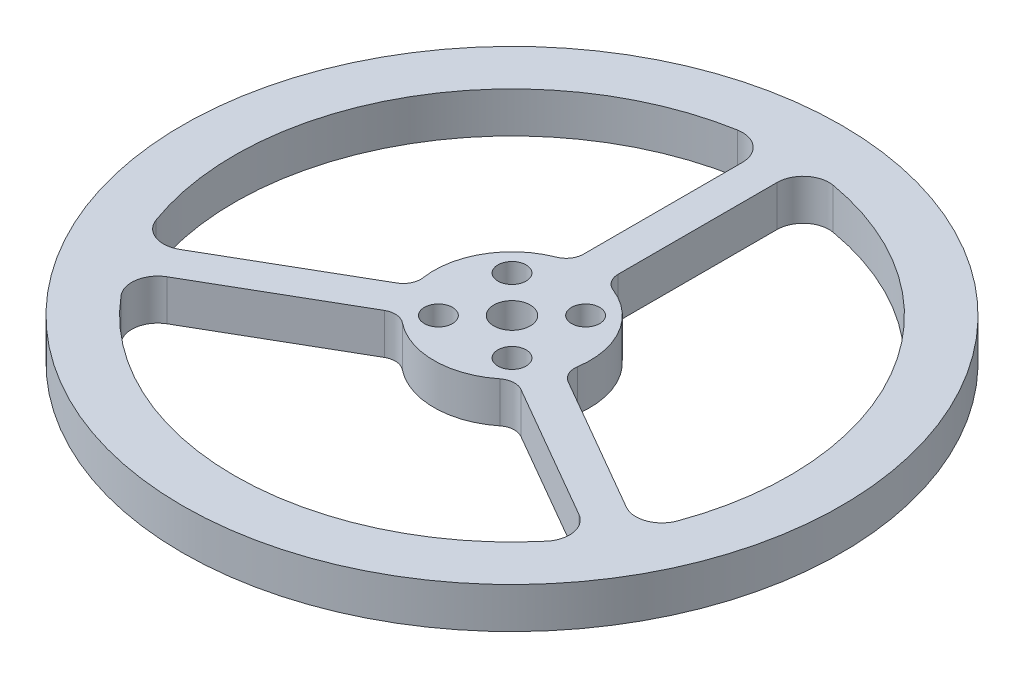
SolidWorks part; units mm, degrees
ref_plane "Front Plane" through (0, 0, 0) normal (0, 0, 1) x (1, 0, 0)
ref_plane "Top Plane" through (0, 0, 0) normal (0, 1, 0) x (1, 0, 0)
ref_plane "Right Plane" through (0, 0, 0) normal (1, 0, 0) x (0, 0, -1)
sketch "Sketch1" plane through (0, 0, 0) normal (0, 1, 0) x (1, 0, 0)
  line L0 (2, 10.247) -> (2, 28.5657)
  line L1 (-2, 10.247) -> (-2, 28.5657)
  line L6 (-4.2426, 4.2426) -> (4.2426, -4.2426) construction
  line L7 (-4.2426, -4.2426) -> (4.2426, 4.2426) construction
  line L8 (0, 28.5657) -> (0, 0) construction
  line L9 (-2, 28.5657) -> (2, 28.5657) construction
  line L10 (9.8741, -3.3914) -> (25.7386, -12.5508)
  line L11 (7.8741, -6.8555) -> (23.7386, -16.0149)
  line L12 (-7.8741, -6.8555) -> (-23.7386, -16.0149)
  line L13 (-9.8741, -3.3914) -> (-25.7386, -12.5508)
  line L14 (0, 0) -> (-32.909, -19) construction
  line L15 (0, 0) -> (32.909, -19) construction
  circle A1 centre (0, 0) radius 38
  arc A3 (-5.5172, 31.5208) -> (-30.0564, -10.9823) centre (0, 0) ccw
  arc A4 (-3.2727, 8.3839) -> (-8.897, -1.3577) centre (0, 0) ccw
  arc A5 (8.0989, 3.9253) -> (3.2727, 8.3839) centre (0, 0) ccw
  circle A7 centre (0, 0) radius 2.1
  arc A8 (-2, 28.5657) -> (-5.5172, 31.5208) centre (-5, 28.5657) ccw
  arc A9 (2, 28.5657) -> (5.5172, 31.5208) centre (5, 28.5657) cw
  arc A14 (-2, 10.247) -> (-3.2727, 8.3839) centre (-4, 10.247) cw
  arc A15 (3.2727, 8.3839) -> (2, 10.247) centre (4, 10.247) cw
  circle A20 centre (-4.2426, 4.2426) radius 1.625
  circle A21 centre (-4.2426, -4.2426) radius 1.625
  circle A22 centre (4.2426, -4.2426) radius 1.625
  circle A23 centre (4.2426, 4.2426) radius 1.625
  arc A24 (9.8741, -3.3914) -> (8.897, -1.3577) centre (10.8741, -1.6594) cw
  arc A25 (5.6243, -7.0262) -> (7.8741, -6.8555) centre (6.8741, -8.5876) cw
  arc A26 (23.7386, -16.0149) -> (24.5392, -20.5385) centre (22.2386, -18.613) cw
  arc A27 (25.7386, -12.5508) -> (30.0564, -10.9823) centre (27.2386, -9.9527) ccw
  arc A28 (-7.8741, -6.8555) -> (-5.6243, -7.0262) centre (-6.8741, -8.5876) cw
  arc A29 (-8.897, -1.3577) -> (-9.8741, -3.3914) centre (-10.8741, -1.6594) cw
  arc A30 (-25.7386, -12.5508) -> (-30.0564, -10.9823) centre (-27.2386, -9.9527) cw
  arc A31 (-23.7386, -16.0149) -> (-24.5392, -20.5385) centre (-22.2386, -18.613) ccw
  arc A32 (-24.5392, -20.5385) -> (24.5392, -20.5385) centre (0, 0) ccw
  arc A33 (30.0564, -10.9823) -> (5.5172, 31.5208) centre (0, 0) ccw
  arc A34 (8.897, -1.3577) -> (8.0989, 3.9253) centre (0, 0) ccw
  arc A35 (-5.6243, -7.0262) -> (5.6243, -7.0262) centre (0, 0) ccw
  circle A36 centre (-4.2426, -4.2426) radius 2.95 construction
  circle A37 centre (-4.2426, 4.2426) radius 2.95 construction
  circle A38 centre (4.2426, -4.2426) radius 2.95 construction
  circle A39 centre (4.2426, 4.2426) radius 2.95 construction
  point P44 (0, 0)
  point P45 (0, 0)
  point P55 (0, 0)
  point P59 (0, 0)
  dimension "D1" = 3
  dimension "D2" = 4.2
  dimension "D3" = 76
  dimension "D4" = 3.25
  dimension "D5" = 12
  dimension "D6" = 9
  dimension "D7" = 4
  dimension "D8" = 32
  dimension "D9" = 2
  dimension "D10" = 3
  dimension "D11" = 120
  dimension "D12" = 120
  dimension "D13" = 5.9
  dimension "D14" = 45
extrude "Boss-Extrude1" add sketch "Sketch1" along normal blind 4.7
